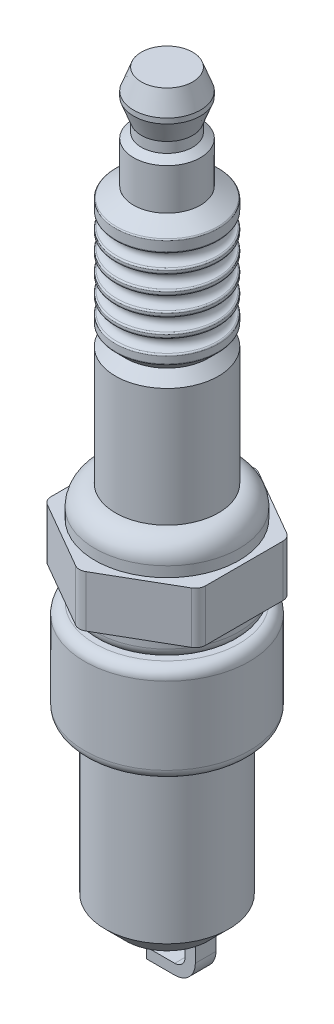
SolidWorks part; units mm, degrees
ref_plane "Front Plane" through (0, 0, 0) normal (0, 0, 1) x (1, 0, 0)
ref_plane "Top Plane" through (0, 0, 0) normal (0, 1, 0) x (1, 0, 0)
ref_plane "Right Plane" through (0, 0, 0) normal (1, 0, 0) x (0, 0, -1)
sketch "Sketch1" plane through (0, 0, 0) normal (0, 0, 1) x (1, 0, 0)
  line L0 (0, 0) -> (0, 75) construction
  line L1 (0, 75) -> (2.5, 75)
  line L2 (2.5, 75) -> (3.25, 73)
  line L5 (3.25, 69) -> (3.25, 65)
  line L6 (3.25, 65) -> (0, 65)
  line L7 (0, 65) -> (0, 75)
  line L8 (3.25, 73) -> (3.25, 72.5)
  line L9 (3.25, 72.5) -> (2.5, 70.5)
  line L10 (2.5, 70.5) -> (2.5, 69.5)
  line L11 (2.5, 69.5) -> (3.25, 69)
  dimension "D1" = 75
  dimension "D2" = 2.5
  dimension "D3" = 3.25
  dimension "D4" = 10
  dimension "D5" = 4
  dimension "D6" = 0.5
  dimension "D7" = 2
  dimension "D8" = 1
revolve "Revolve1" add sketch "Sketch1" angle 360 about L7
sketch "Sketch2" plane through (0, 0, 0) normal (0, 0, 1) x (1, 0, 0)
  line L0 (0, 0) -> (0, 75) construction
  line L1 (2.5, 75) -> (-2.5, 75) construction
  line L2 (0, 65) -> (0, 40)
  line L3 (-3.25, 65) -> (3.25, 65) construction
  line L4 (0, 40) -> (5, 40)
  line L5 (5, 40) -> (5, 51.5)
  line L6 (0, 65) -> (3.25, 65)
  line L7 (3.25, 65) -> (4.9244, 64.0432)
  line L8 (5, 63.913) -> (5, 62.9858)
  line L9 (5, 51.5) -> (4, 52.5)
  line L10 (4, 52.5) -> (4.9561, 53.4561)
  line L11 (5, 61.4142) -> (5, 61.1858)
  line L12 (5, 59.6142) -> (5, 59.3858)
  line L13 (5, 57.8142) -> (5, 57.5858)
  line L14 (5, 56.0142) -> (5, 55.7858)
  line L15 (5, 54.2142) -> (5, 53.5621)
  arc A0 (4.8781, 55.6385) -> (4.8781, 54.3615) centre (5, 55) ccw
  arc A1 (4.8781, 57.4385) -> (4.8781, 56.1615) centre (5, 56.8) ccw
  arc A2 (4.8781, 59.2385) -> (4.8781, 57.9615) centre (5, 58.6) ccw
  arc A3 (4.8781, 61.0385) -> (4.8781, 59.7615) centre (5, 60.4) ccw
  arc A4 (4.8781, 62.8385) -> (4.8781, 61.5615) centre (5, 62.2) ccw
  arc A5 (5, 53.5621) -> (4.9561, 53.4561) centre (4.85, 53.5621) cw
  arc A6 (5, 54.2142) -> (4.8781, 54.3615) centre (4.85, 54.2142) ccw
  arc A7 (5, 55.7858) -> (4.8781, 55.6385) centre (4.85, 55.7858) cw
  arc A8 (5, 56.0142) -> (4.8781, 56.1615) centre (4.85, 56.0142) ccw
  arc A9 (5, 57.5858) -> (4.8781, 57.4385) centre (4.85, 57.5858) cw
  arc A10 (5, 57.8142) -> (4.8781, 57.9615) centre (4.85, 57.8142) ccw
  arc A11 (5, 59.3858) -> (4.8781, 59.2385) centre (4.85, 59.3858) cw
  arc A12 (5, 59.6142) -> (4.8781, 59.7615) centre (4.85, 59.6142) ccw
  arc A13 (5, 61.1858) -> (4.8781, 61.0385) centre (4.85, 61.1858) cw
  arc A14 (5, 61.4142) -> (4.8781, 61.5615) centre (4.85, 61.4142) ccw
  arc A15 (5, 62.9858) -> (4.8781, 62.8385) centre (4.85, 62.9858) cw
  arc A16 (4.9244, 64.0432) -> (5, 63.913) centre (4.85, 63.913) cw
  point P55 (5, 64)
  dimension "D12" = 1.3
  dimension "D13" = 0.15
  dimension "D1" = 25
  dimension "D2" = 11.5
  dimension "D3" = 5
  dimension "D4" = 12.5
  dimension "D5" = 1
  dimension "D6" = 4
  dimension "D7" = 1.8
  dimension "D8" = 1.8
  dimension "D9" = 1.8
  dimension "D10" = 1.8
  dimension "D11" = 1.8
revolve "Revolve2" add sketch "Sketch2" angle 360 about L2
sketch "Sketch3" plane through (0, 0, 0) normal (0, 0, 1) x (1, 0, 0)
  line L0 (0, 0) -> (0, 75) construction
  line L1 (2.5, 75) -> (-2.5, 75) construction
  line L2 (-5, 40) -> (5, 40) construction
  line L3 (7, 38) -> (7, 31)
  line L4 (6, 30) -> (0, 30)
  line L5 (0, 30) -> (0, 40)
  line L6 (0, 40) -> (5, 40)
  line L7 (5, 40) -> (5, 51.5) construction
  arc A0 (5, 40) -> (7, 38) centre (5, 38) cw
  arc A1 (7, 31) -> (6, 30) centre (6, 31) cw
  dimension "D3" = 1
  dimension "D1" = 10
  dimension "D2" = 7
revolve "Revolve3" add sketch "Sketch3" angle 360 about L5
sketch "Sketch4" plane through (0, 0, 0) normal (0, 0, 1) x (1, 0, 0)
  line L0 (0, 0) -> (0, 75) construction
  line L1 (2.5, 75) -> (-2.5, 75) construction
  line L2 (0, 30) -> (0, 20.5)
  line L3 (-6, 30) -> (6, 30) construction
  line L4 (0, 30) -> (7, 30)
  line L5 (8, 29) -> (8, 21.5)
  line L6 (7, 20.5) -> (0, 20.5)
  arc A0 (8, 21.5) -> (7, 20.5) centre (7, 21.5) cw
  arc A1 (7, 30) -> (8, 29) centre (7, 29) cw
  dimension "D3" = 1
  dimension "D1" = 9.5
  dimension "D2" = 8
revolve "Revolve4" add sketch "Sketch4" angle 360 about L2
sketch "Sketch5" plane through (0, 0, 0) normal (0, 0, 1) x (1, 0, 0)
  line L0 (0, 0) -> (0, 75) construction
  line L1 (2.5, 75) -> (-2.5, 75) construction
  line L2 (0, 20.5) -> (0, 3.5)
  line L3 (-7, 20.5) -> (7, 20.5) construction
  line L4 (0, 3.5) -> (4, 3.5)
  line L5 (6, 5.5) -> (6, 20.5)
  line L6 (6, 20.5) -> (0, 20.5)
  line L7 (4, 3.5) -> (6, 5.5)
  point P10 (6, 3.5)
  dimension "D1" = 6
  dimension "D2" = 17
revolve "Revolve5" add sketch "Sketch5" angle 360 about L2
ref_plane "Plane1" through (0, 32, 0) normal (0, 1, 0) x (1, 0, 0)
sketch "Sketch6" plane through (0, 32, 0) normal (0, 1, 0) x (1, 0, 0)
  line L1 (0, 8.6603) -> (-7.5, 4.3301)
  line L2 (-7.5, 4.3301) -> (-7.5, -4.3301)
  line L3 (-7.5, -4.3301) -> (0, -8.6603)
  line L4 (0, -8.6603) -> (7.5, -4.3301)
  line L5 (7.5, -4.3301) -> (7.5, 4.3301)
  line L6 (7.5, 4.3301) -> (0, 8.6603)
  circle A0 centre (0, 0) radius 7.5 construction
  dimension "D1" = 15
extrude "Boss-Extrude1" add sketch "Sketch6" along normal blind 5 separate body
fillet "Fillet1" radius 1 6 edges at (-7.5, 34.5, -4.3301) (0, 34.5, -8.6603) (7.5, 34.5, -4.3301) (-7.5, 34.5, 4.3301) (7.5, 34.5, 4.3301) (0, 34.5, 8.6603)
sketch "Sketch7" plane through (0, 0, 0) normal (0, 0, 1) x (1, 0, 0)
  line L0 (-1, 0) -> (1.75, 0)
  line L1 (3.75, 3.5) -> (3.75, 2)
  line L2 (-4, 3.5) -> (4, 3.5) construction
  line L3 (-1, 0) -> (-1, 1)
  line L4 (-1, 1) -> (1.75, 1)
  line L6 (2.75, 3.5) -> (3.75, 3.5)
  line L7 (2.75, 3.5) -> (2.75, 2)
  arc A0 (1.75, 0) -> (3.75, 2) centre (1.75, 2) ccw
  arc A1 (1.75, 1) -> (2.75, 2) centre (1.75, 2) ccw
  point P12 (0, 0)
  dimension "D4" = 2
  dimension "D1" = 1
  dimension "D2" = 1
  dimension "D3" = 3.75
  dimension "D5" = 1
extrude "Boss-Extrude2" add sketch "Sketch7" along normal blind 1 and the other way blind 1
equation "\"D8@Sketch2\"=\"D7@Sketch2\""
equation "\"D9@Sketch2\"=\"D7@Sketch2\""
equation "\"D10@Sketch2\"=\"D7@Sketch2\""
equation "\"D11@Sketch2\"=\"D7@Sketch2\""
